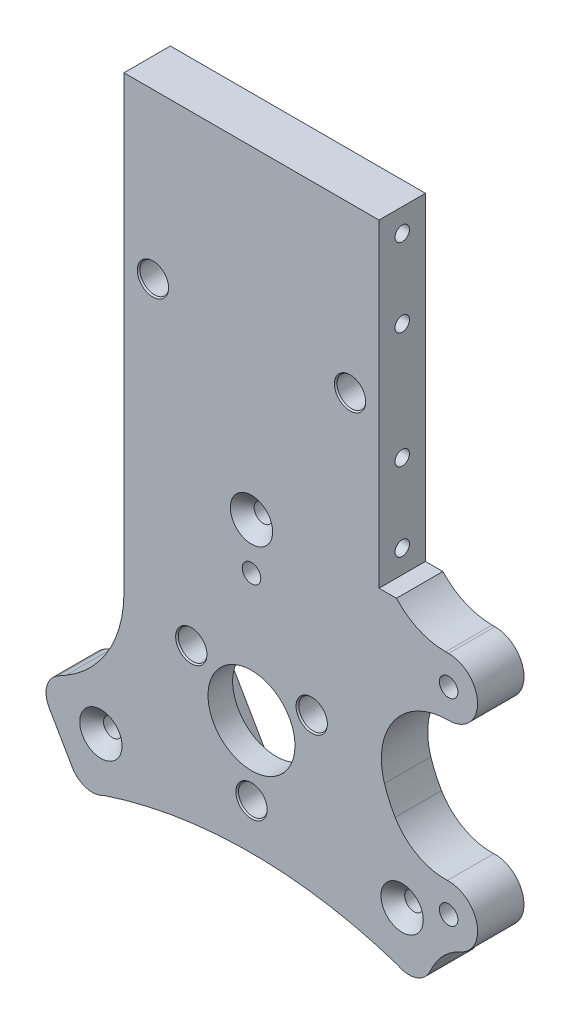
SolidWorks part; units mm, degrees
ref_plane "Front Plane" through (0, 0, 0) normal (0, 0, 1) x (1, 0, 0)
ref_plane "Top Plane" through (0, 0, 0) normal (0, 1, 0) x (1, 0, 0)
ref_plane "Right Plane" through (0, 0, 0) normal (1, 0, 0) x (0, 0, -1)
sketch "Sketch1" plane through (0, 0, 0) normal (0, 0, 1) x (1, 0, 0)
  line L0 (-1000, 0) -> (49000, 0) construction
  line L1 (0, -1000) -> (0, 49000) construction
  line L2 (0, 0) -> (-37.6779, -21.7533) construction
  line L3 (0, 0) -> (34.4865, -19.9108) construction
  line L4 (10, -8.7457) -> (10, 8.7457) construction
  line L5 (10.3863, 10.4956) -> (-10.3863, 10.4956)
  line L6 (-14.2847, 3.7444) -> (-3.9035, -14.2421)
  line L7 (3.9036, -14.242) -> (14.2846, 3.7447)
  line L8 (9.0941, -5.2486) -> (-10.3863, 5.9944) construction
  line L9 (0, -11.9891) -> (0, 10.4956) construction
  line L10 (10.3863, 5.9946) -> (-9.0941, -5.2488) construction
  line L11 (-30.909, -22.4641) -> (-34.909, -15.5359)
  line L12 (-32, -9.2376) -> (-33.4449, -10.0718)
  line L13 (-25, -23.6714) -> (-25.4449, -23.9282)
  line L14 (24.7944, -23.6821) -> (25.2453, -23.9282)
  line L15 (30.7512, -22.1827) -> (34.3345, -14.8973)
  line L16 (22, 49.7573) -> (-22, 49.7573)
  line L17 (22, 49.7573) -> (22, 38.5054)
  line L18 (32, -9.2376) -> (32.7451, -9.6678)
  line L19 (-22, 49.7573) -> (-22, 8.0829)
  line L20 (-4, 6.9282) -> (-41.6779, -14.8251) construction
  line L21 (34, 27.0109) -> (33.4945, 27.0109)
  line L22 (34, 17.0109) -> (33.8909, 17.0109)
  line L25 (-12, 0) -> (-12.0927, -0.0535)
  circle A0 centre (0, 0) radius 30 construction
  circle A1 centre (0, 0) radius 7.5
  circle A2 centre (0, 30) radius 4 construction
  circle A3 centre (25.9808, -15) radius 4 construction
  circle A4 centre (-25.9808, -15) radius 4 construction
  arc A5 (-10.3863, 10.4956) -> (-14.2847, 3.7444) centre (-10.3863, 5.9944) ccw
  arc A6 (-3.9035, -14.2421) -> (3.9036, -14.242) centre (0, -11.9891) ccw
  arc A7 (14.2846, 3.7447) -> (10.3863, 10.4956) centre (10.3863, 5.9946) ccw
  circle A8 centre (27.3746, 42.204) radius 2.5
  circle A9 centre (-27.6254, 42.204) radius 2.5
  arc A10 (32, -9.2376) -> (22.9322, 2.0481) centre (42, 8.0829) cw
  arc A11 (-22, 8.0829) -> (-32, -9.2376) centre (-42, 8.0829) cw
  arc A12 (25.2453, -23.9282) -> (-25.4449, -23.9282) centre (-0.0998, -99.8072) ccw
  arc A13 (30.7512, -22.1827) -> (25.2453, -23.9282) centre (27.1619, -20.4173) cw
  arc A14 (32.7451, -9.6678) -> (34.3345, -14.8973) centre (30.7451, -13.1319) cw
  arc A15 (-30.909, -22.4641) -> (-25.4449, -23.9282) centre (-27.4449, -20.4641) ccw
  arc A16 (-33.4449, -10.0718) -> (-34.909, -15.5359) centre (-31.4449, -13.5359) ccw
  circle A17 centre (34, -11.9891) radius 5
  arc A18 (34, 17.0109) -> (34, 27.0109) centre (34, 22.0109) ccw
  arc A19 (22, 38.5054) -> (33.4945, 27.0109) centre (33.4945, 38.5054) ccw
  arc A20 (33.8909, 17.0109) -> (22.9322, 2.0481) centre (33.8909, 5.5165) ccw
  point P4 (0, 0)
  point P19 (0, 0)
  point P21 (10, 0)
  point P40 (0, 0.9917)
  point P46 (0, 49.7573)
  point P47 (-32.909, -19)
  point P62 (28.909, -25.9282)
  point P67 (-28.909, -25.9282)
  line B0 (37, -11.9891) -> (-75, -11.9891) construction
  line B1 (0, -11.9891) -> (0, 22.0109) construction
  line B2 (-14.25, -36.1891) -> (-14.25, -11.9891) construction
  line B3 (-29.75, -13.311) -> (-29.75, -10.6672) construction
  line B4 (-39.75, -13.2558) -> (-39.75, -10.7223) construction
  line B5 (34, -11.9891) -> (34, 22.0109) construction
  line B6 (37, 27.0109) -> (37, -16.9891) construction
  line B7 (37, 27.0109) -> (-3, 27.0109) construction
  line B8 (37, -16.9891) -> (-3, -16.9891) construction
  line B9 (-14.25, -11.9891) -> (-14.25, 75.8256) construction
  line B10 (-3, 27.0109) -> (-3, -16.9891) construction
  dimension "D1" = 60
  dimension "D4" = 15
  dimension "D5" = 3
  dimension "D7" = 55
  dimension "D9" = 8
  dimension "D11" = 20
  dimension "D12" = 11.4945
  dimension "D13" = 4
  dimension "D14" = 4
  dimension "D15" = 11.4945
  dimension "D2" = 120
  dimension "D3" = 120
  dimension "D6" = 10
  dimension "D8" = 44
  dimension "D10" = 8
sketch_block_instance "HemeraFrontContraints-3"
sketch_block "HemeraFrontContraints" parameters "D1"=34, "D2"=48.25, "D3"=63.75, "D4"=73.75, "D5"=24.2, "D6"=34, "D7"=34, "D8"=31.699, "D9"=36.9763, "D10"=44
sketch "Sketch2" plane through (0, 0, 0) normal (0, 1, 0) x (1, 0, 0)
  line L0 (52, -10) -> (52, -104) construction
  line L1 (-49, 0) -> (49, 0) construction
  line L2 (-52, -10) -> (-52, -104) construction
  line L3 (-52, -104) -> (52, -104) construction
  line L4 (0, 0) -> (0, -30) construction
  line L7 (-52, -10) -> (-49, -10) construction
  line L8 (-49, 0) -> (-49, -10) construction
  line L11 (52, -10) -> (49, -10) construction
  line L12 (49, 0) -> (49, -10) construction
  point P12 (0, -104)
  dimension "D1" = 98
  dimension "D2" = 104
  dimension "D3" = 30
  dimension "D4" = 10
  dimension "D7" = 104
extrude "Boss-Extrude1" add sketch "Sketch1" along normal blind 8 contours A7 L7 A6 L6 A5 L5 | L17 | L19 | L16 L19 L17 | A10 A17 L15 A14 L18 | L15 A17 A10 L18 A14 region at (1.5486, 13.9173, 0) region at (31.8342, -12.7141, 0) region at (35.6729, -11.4291, 0)
extrude "Boss-Extrude2" add sketch "Sketch1<3>" along normal blind 4.25 from offset 3.75 contours L7 A7 L5 A5 L6 A6 A1 region at (13.936, 8.0445, 0)
sketch "Sketch1<3>" plane through (0, 0, 0) normal (0, 0, 1) x (1, 0, 0) same geometry as "Sketch1"
sketch "Sketch15" plane through (0, 49.7573, 0) normal (0, 1, 0) x (1, 0, 0)
  line L4 (22, 0) -> (-22, 0)
  line L5 (-22, 0) -> (-22, -8)
  line L6 (-22, -8) -> (22, -8)
  line L7 (22, -8) -> (22, 0)
  line L8 (22, 0) -> (-22, 0)
  line L9 (-22, 0) -> (-22, -8)
  line L10 (-22, -8) -> (22, -8)
  line L11 (22, -8) -> (22, 0)
  dimension "D1" = 0
extrude "Boss-Extrude3" add sketch "Sketch15" along normal blind 36
sketch "Sketch4" plane through (0, 0, 0) normal (0, 0, -1) x (-1, 0, 0)
  line L0 (0, 26) -> (0, 34)
  arc A0 (0, 26) -> (0, 34) centre (0, 30) ccw
revolve "Cut-Revolve1" cut sketch "Sketch4" angle 360 about L0
sketch "Sketch22" plane through (0, 0, 8) normal (0, 0, 1) x (1, 0, 0)
  line L0 (22, 49.7573) -> (22, 38.5054) construction
  line L1 (22, 40.7573) -> (27, 40.7573)
  line L2 (22, 40.7573) -> (22, 30.7573)
  line L3 (22, 30.7573) -> (27, 30.7573)
  line L4 (27, 40.7573) -> (27, 30.7573)
  dimension "D1" = 10
  dimension "D2" = 5
  dimension "D3" = 30.7573
extrude "Cut-Extrude1" cut sketch "Sketch22" against normal blind 10
sketch "Sketch5" plane through (0, 0, 0) normal (0, 0, -1) x (-1, 0, 0)
  line L0 (-22.5167, -13) -> (-29.4449, -17)
  line L1 (0, 0) -> (-34.4865, -19.9108) construction
  arc A0 (-22.5167, -13) -> (-29.4449, -17) centre (-25.9808, -15) ccw
revolve "Cut-Revolve2" cut sketch "Sketch5" angle 360 about L0
sketch "Sketch6" plane through (0, 0, 0) normal (0, 0, -1) x (-1, 0, 0)
  line L0 (22.5167, -13) -> (29.4449, -17)
  line L1 (0, 0) -> (37.6779, -21.7533) construction
  arc A0 (22.5167, -13) -> (29.4449, -17) centre (25.9808, -15) ccw
revolve "Cut-Revolve3" cut sketch "Sketch6" angle 360 about L0
hole_wizard "CSK for M3 Flat Head Machine Screw1" positions "Sketch7" profile "Sketch8" countersink size "M3" standard "ANSI Metric" end condition through all
sketch "Sketch7" plane through (0, 0, 8) normal (0, 0, 1) x (1, 0, 0)
  point P0 (0, 30)
  point P3 (25.9808, -15)
  point P6 (-25.9808, -15)
sketch "Sketch8" plane through (0, 30, 8) normal (1, 0, 0) x (0, -1, 0)
  line L0 (0, 0) -> (0, 8)
  line L1 (0, 8) -> (1.6, 8)
  line L2 (1.6, 8) -> (1.6, 2.05)
  line L3 (1.6, 2.05) -> (3.65, 0)
  line L5 (3.65, 0) -> (0, 0)
  line L6 (-1.6, 2.05) -> (-3.65, 0) construction
  line L11 (0, -6.35) -> (0, 107.95) construction
  dimension "Thru Hole Dia." = 3.2
  dimension "Thru Hole Depth" = 8
  dimension "Near C'Sink Dia." = 7.3
  dimension "Near C'Sink Angle" = 90
hole_wizard "CBORE for M3 SBHCS2" positions "Sketch11" profile "Sketch12" counterbore size "M3" standard "ANSI Metric" end condition through all
sketch "Sketch11" plane through (0, 0, 0) normal (0, 0, -1) x (-1, 0, 0)
  point P0 (-34, 22.0109)
  point P3 (0, 22.0109)
  point P6 (0, -11.9891)
  point P19 (-34, -11.9891)
sketch "Sketch12" plane through (34, 22.0109, 0) normal (1, 0, 0) x (0, 1, 0)
  line L0 (0, 0) -> (0, 8)
  line L1 (0, 8) -> (1.6, 8)
  line L3 (1.6, 8) -> (1.6, 3)
  line L4 (3.35, 3) -> (1.6, 3)
  line L5 (3.35, 3) -> (3.35, 0.025)
  line L6 (3.35, 0.025) -> (3.375, 0)
  line L7 (3.375, 0) -> (0, 0)
  line L8 (-3.35, 0.025) -> (-3.375, 0) construction
  line L11 (0, -6.35) -> (0, 107.95) construction
  dimension "Thru Hole Dia." = 3.2
  dimension "Thru Hole Depth" = 8
  dimension "C'Bore Dia." = 6.7
  dimension "C'Bore Depth" = 3
  dimension "Near C'Sink Dia." = 6.75
  dimension "Near C'Sink Angle" = 90
hole_wizard "CSK for M4 Flat Head Machine Screw1" positions "Sketch13" profile "Sketch14" countersink size "M4" standard "ANSI Metric" end condition through all
sketch "Sketch13" plane through (0, 0, 8) normal (0, 0, 1) x (1, 0, 0)
  point P0 (-10.3863, 5.9944)
  point P3 (10.3863, 5.9946)
  point P6 (0, -11.9891)
sketch "Sketch14" plane through (-10.3863, 5.9944, 8) normal (1, 0, 0) x (0, -1, 0)
  line L0 (0, 0) -> (0, 8)
  line L1 (0, 8) -> (2.5, 8)
  line L2 (2.5, 8) -> (2.5, 0.2606)
  line L3 (2.5, 0.2606) -> (2.7, 0)
  line L5 (2.7, 0) -> (0, 0)
  line L6 (-2.5, 0.2606) -> (-2.7, 0) construction
  line L11 (0, -6.35) -> (0, 107.95) construction
  dimension "Thru Hole Dia." = 5
  dimension "Thru Hole Depth" = 8
  dimension "Near C'Sink Dia." = 5.4
  dimension "Near C'Sink Angle" = 75
fillet "Fillet1" radius 10 2 edges at (30.5834, -8.3385, 4) (33.328, -16.9437, 4)
hole_wizard "Tap Drill for M3x0.5 Tap4" positions "Sketch25" profile "Sketch26" hole size "M3x0.5" standard "ANSI Metric"
sketch "Sketch25" plane through (22, 0, 0) normal (1, 0, 0) x (0, 0, -1)
  line L0 (-8, 85.7573) -> (0, 85.7573) construction
  line L1 (0, 85.7573) -> (0, 30.7573) construction
  point P0 (-4, 81.7573)
  point P2 (-4, 68.2573)
  point P4 (-4, 34.7573)
  point P6 (-4, 48.2573)
  dimension "D1" = 4
  dimension "D2" = 13.5
  dimension "D3" = 13.5
  dimension "D4" = 20
  dimension "D5" = 4
sketch "Sketch26" plane through (22, 81.7573, 4) normal (0, 1, 0) x (0, 0, -1)
  line L0 (0, 0) -> (0, 5.7511)
  line L1 (0, 5.7511) -> (1.25, 5)
  line L2 (1.25, 5) -> (1.25, 0)
  line L5 (1.25, 0) -> (0, 0)
  line L10 (0, 5.7511) -> (-1.25, 5) construction
  line L11 (0, -6.35) -> (0, 107.95) construction
  dimension "Hole Dia." = 2.5
  dimension "Hole Depth" = 5
  dimension "Drill Angle" = 118
mirror "Mirror1" about plane through (0, 0, 0) normal (1, 0, 0) of "Tap Drill for M3x0.5 Tap4"
sketch "Sketch27" plane through (0, 0, 0) normal (0, 0, -1) x (-1, 0, 0)
  line L0 (-22, 70.5898) -> (22, 70.5898) construction
  line L1 (-22, 85.7573) -> (-22, 30.7573) construction
  line L2 (22, 85.7573) -> (22, 8.0829) construction
  text T0 "HEMERA" font "Century Gothic" height 7.5
extrude "Cut-Extrude2" cut sketch "Sketch27" against normal blind 1
sketch "Sketch28" plane through (0, 0, 8) normal (0, 0, 1) x (1, 0, 0)
  line L1 (0, -914.2427) -> (0, 49085.7573) construction
  line L2 (-22, 85.7573) -> (22, 85.7573) construction
  line L3 (-22, 85.7573) -> (-22, 8.0829) construction
  line L4 (-22, 81.0862) -> (22, 81.0862) construction
  line L6 (-22, 81.0862) -> (-22, 53.0862) construction
  line L7 (-22, 53.0862) -> (22, 53.0862) construction
  line L8 (22, 81.0862) -> (22, 53.0862) construction
  line L9 (22, 85.7573) -> (22, 30.7573) construction
  point P5 (0, 85.7573)
  dimension "D1" = 28
hole_wizard "CSK for M4 Flat Head Machine Screw2" positions "Sketch29" profile "Sketch30" countersink size "M4" standard "ANSI Metric" end condition through all
sketch "Sketch29" plane through (0, 0, 8) normal (0, 0, 1) x (1, 0, 0)
  line L0 (0, -200914.2427) -> (0, 249085.7573) construction
  point P0 (-17, 57.4551)
  point P2 (17, 57.4551)
  dimension "D1" = 34
  dimension "D2" = 17
sketch "Sketch30" plane through (-17, 57.4551, 8) normal (1, 0, 0) x (0, -1, 0)
  line L0 (0, 0) -> (0, 8)
  line L1 (0, 8) -> (2.5, 8)
  line L2 (2.5, 8) -> (2.5, 0.2606)
  line L3 (2.5, 0.2606) -> (2.7, 0)
  line L5 (2.7, 0) -> (0, 0)
  line L6 (-2.5, 0.2606) -> (-2.7, 0) construction
  line L11 (0, -6.35) -> (0, 107.95) construction
  dimension "Thru Hole Dia." = 5
  dimension "Thru Hole Depth" = 8
  dimension "Near C'Sink Dia." = 5.4
  dimension "Near C'Sink Angle" = 75
